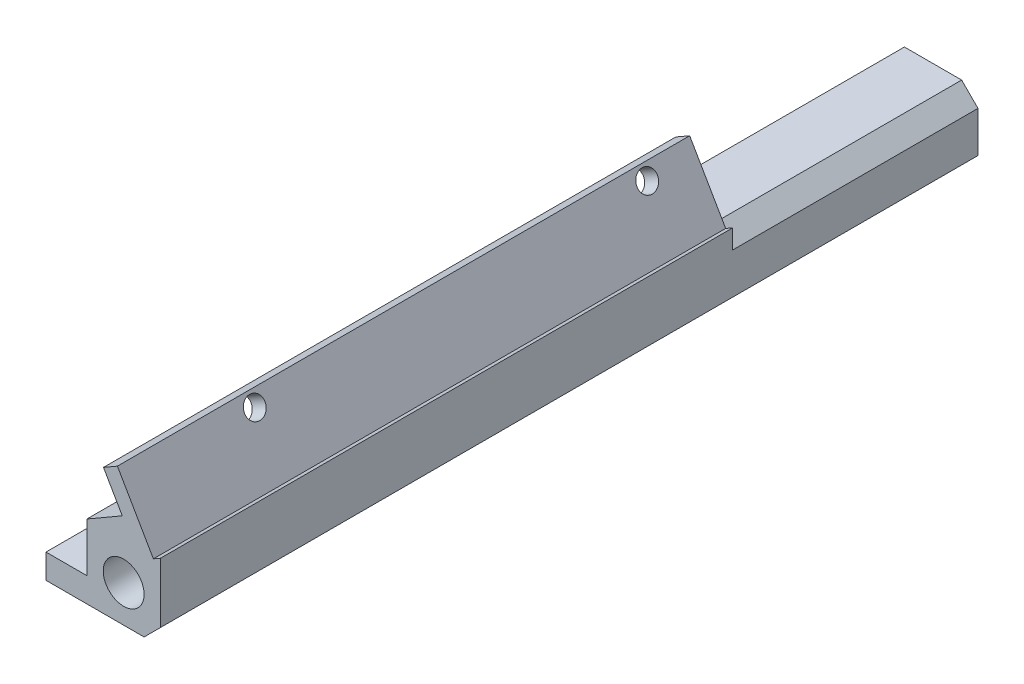
SolidWorks part; units mm, degrees
ref_plane "Front Plane" through (0, 0, 0) normal (0, 0, 1) x (1, 0, 0)
ref_plane "Top Plane" through (0, 0, 0) normal (0, 1, 0) x (1, 0, 0)
ref_plane "Right Plane" through (0, 0, 0) normal (1, 0, 0) x (0, 0, -1)
sketch "Sketch1" plane through (0, 0, 0) normal (0, 1, 0) x (1, 0, 0)
  line L1 (0, 0) -> (77.47, 0)
  line L2 (0, 0) -> (0, 127)
  line L3 (0, 127) -> (77.47, 127)
  line L4 (77.47, 0) -> (77.47, 127)
  dimension "D1" = 77.47
  dimension "D2" = 127
extrude "Boss-Extrude1" add sketch "Sketch1" along normal blind 11.43
sketch "Sketch2" plane through (0, 0, 0) normal (0, 0, 1) x (1, 0, 0)
  line L0 (5.715, 5.715) -> (71.755, 5.715) construction
  line L1 (38.735, 11.43) -> (38.735, 0) construction
  line L2 (0, 11.43) -> (77.47, 11.43) construction
  line L3 (0, 0) -> (77.47, 0) construction
  circle A0 centre (5.715, 5.715) radius 3.175
  circle A1 centre (71.755, 5.715) radius 3.175
  point P10 (38.735, 5.715)
  dimension "D1" = 6.35
  dimension "D2" = 66.04
extrude "Cut-Extrude1" cut sketch "Sketch2" against normal through all
sketch "Sketch3" plane through (0, 11.43, 0) normal (0, 1, 0) x (1, 0, 0)
  line L0 (11.43, 127) -> (11.43, 88.9)
  line L1 (77.47, 127) -> (0, 127) construction
  line L2 (11.43, 127) -> (66.04, 127)
  line L3 (66.04, 127) -> (66.04, 88.9)
  line L4 (53.34, 76.2) -> (24.13, 76.2)
  line L5 (0, 127) -> (0, 0) construction
  arc A0 (66.04, 88.9) -> (53.34, 76.2) centre (53.34, 88.9) cw
  arc A1 (24.13, 76.2) -> (11.43, 88.9) centre (24.13, 88.9) cw
  point P10 (38.735, 127)
  dimension "D1" = 12.7
  dimension "D2" = 11.43
  dimension "D3" = 50.8
extrude "Cut-Extrude2" cut sketch "Sketch3" against normal through all
sketch "Sketch4" plane through (0, 0, -127) normal (0, 0, -1) x (-1, 0, 0)
  line L0 (-11.43, 0) -> (-11.43, 11.43) construction
  line L1 (-66.04, 11.43) -> (-11.43, 11.43)
  line L2 (-66.04, 11.43) -> (-66.04, 5.08)
  line L3 (-66.04, 5.08) -> (-11.43, 5.08)
  line L4 (-11.43, 11.43) -> (-11.43, 5.08)
  line L5 (-11.43, 0) -> (0, 0) construction
  dimension "D1" = 5.08
extrude "Cut-Extrude3" cut sketch "Sketch4" against normal through all
chamfer "Chamfer1" distance 2.54 angle 45 4 edges at (0, 0, -63.5) (0, 11.43, -63.5) (77.47, 0, -63.5) (77.47, 11.43, -63.5)
sketch "Sketch5" plane through (0, 11.43, 0) normal (0, 1, 0) x (1, 0, 0)
  line L0 (66.04, 76.2) -> (0, 76.2)
  line L1 (66.04, 0) -> (66.04, 88.9) construction
  line L2 (0, 0) -> (0, 127) construction
  line L3 (0, 76.2) -> (0, 127)
  line L4 (0, 127) -> (66.04, 127)
  line L5 (66.04, 127) -> (66.04, 76.2)
  line L6 (24.13, 76.2) -> (53.34, 76.2) construction
extrude "Cut-Extrude4" cut sketch "Sketch5" against normal through all
sketch "Sketch6" plane through (0, 11.43, 0) normal (0, 1, 0) x (1, 0, 0)
  line L0 (53.34, 76.2) -> (53.34, 0)
  line L1 (11.43, 76.2) -> (66.04, 76.2) construction
  line L2 (66.04, 0) -> (11.43, 0) construction
  line L3 (53.34, 0) -> (0, 0)
  line L4 (0, 0) -> (0, 76.2)
  line L5 (0, 76.2) -> (53.34, 76.2)
  line L6 (66.04, 0) -> (66.04, 127) construction
  dimension "D1" = 12.7
extrude "Cut-Extrude5" cut sketch "Sketch6" against normal through all
sketch "Sketch7" plane through (0, 5.08, 0) normal (0, 1, 0) x (1, 0, 0)
  line L0 (53.34, 76.2) -> (66.04, 76.2) construction
  line L1 (66.04, 0) -> (66.04, 76.2) construction
  circle A0 centre (62.23, 68.58) radius 1.5875
  circle A4 centre (62.23, 7.62) radius 1.5875
  point P5 (0, 0)
  dimension "D1" = 3.175
  dimension "D2" = 7.62
  dimension "D3" = 68.58
  dimension "D4" = 3.81
extrude "Cut-Extrude6" cut sketch "Sketch7" against normal through all
sketch "Sketch8" plane through (0, 0, 0) normal (0, 0, 1) x (1, 0, 0)
  line L0 (77.47, 11.8699) -> (77.47, 7.0306)
  line L1 (77.47, 11.8699) -> (71.882, 21.5486)
  line L2 (71.882, 21.5486) -> (68.6183, 19.6643)
  line L3 (68.6183, 19.6643) -> (71.5393, 14.605)
  line L4 (71.5393, 14.605) -> (66.04, 11.43)
  line L5 (77.47, 11.43) -> (68.58, 11.43) construction
  line L6 (66.04, 11.43) -> (74.93, 11.43) construction
  line L7 (66.04, 11.43) -> (74.93, 11.43)
  line L8 (74.93, 11.43) -> (77.47, 7.0306)
  line L9 (77.47, 8.89) -> (77.47, 2.54) construction
  point P0 (0, 0)
  dimension "D2" = 11.176
  dimension "D3" = 6.35
  dimension "D4" = 5.842
  dimension "D6" = 60
extrude "Boss-Extrude2" add sketch "Sketch8" against normal blind 88.9
sketch "Sketch9" plane through (0, 0, 0) normal (0, 0, 1) x (1, 0, 0)
  line L0 (74.93, 0) -> (66.04, 0) construction
  line L1 (53.34, 0) -> (74.93, 0) construction
  line L3 (66.04, 0) -> (59.69, 0) construction
  line L4 (59.69, 0) -> (53.34, 0)
  line L5 (53.34, 0) -> (53.34, 5.08)
  line L6 (53.34, 5.08) -> (59.69, 5.08)
  line L7 (66.04, 5.08) -> (53.34, 5.08) construction
  line L8 (59.69, 5.08) -> (59.69, 0)
  dimension "D1" = 6.35
extrude "Cut-Extrude7" cut sketch "Sketch9" against normal up to next
sketch "Sketch10" plane through (0, 0, 0) normal (0, 0, 1) x (1, 0, 0)
  line L0 (59.69, 5.08) -> (66.04, 5.08)
  line L1 (66.04, 5.08) -> (66.04, 3.81)
  line L2 (66.04, 3.81) -> (59.69, 3.81)
  line L3 (59.69, 0) -> (59.69, 5.08) construction
  line L4 (59.69, 3.81) -> (59.69, 5.08)
  line L5 (59.69, 0) -> (74.93, 0) construction
  dimension "D1" = 3.81
extrude "Cut-Extrude8" cut sketch "Sketch10" against normal up to next
sketch "Sketch11" plane through (59.9786, 34.6287, 0) normal (-0.866, -0.5, 0) x (0, 0, 1)
  line L0 (-88.9, -23.1213) -> (0, -23.1213) construction
  line L1 (-88.9, -17.2793) -> (-88.9, -23.1213) construction
  circle A0 centre (-20.32, -19.3113) radius 1.5875
  circle A1 centre (-81.28, -19.3113) radius 1.5875
  point P4 (0, 0)
  dimension "D1" = 3.175
  dimension "D2" = 3.81
  dimension "D3" = 7.62
  dimension "D4" = 68.58
extrude "Cut-Extrude9" cut sketch "Sketch11" against normal up to next
sketch "Sketch12" plane through (63.2423, 36.513, 0) normal (0.866, 0.5, 0) x (0, 0, -1)
  line L1 (88.9, -17.2793) -> (0, -17.2793)
  line L2 (88.9, -17.2793) -> (88.9, -28.4553)
  line L3 (88.9, -28.4553) -> (0, -28.4553)
  line L4 (0, -17.2793) -> (0, -28.4553)
extrude "Cut-Extrude10" cut sketch "Sketch12" against normal blind 1.27
